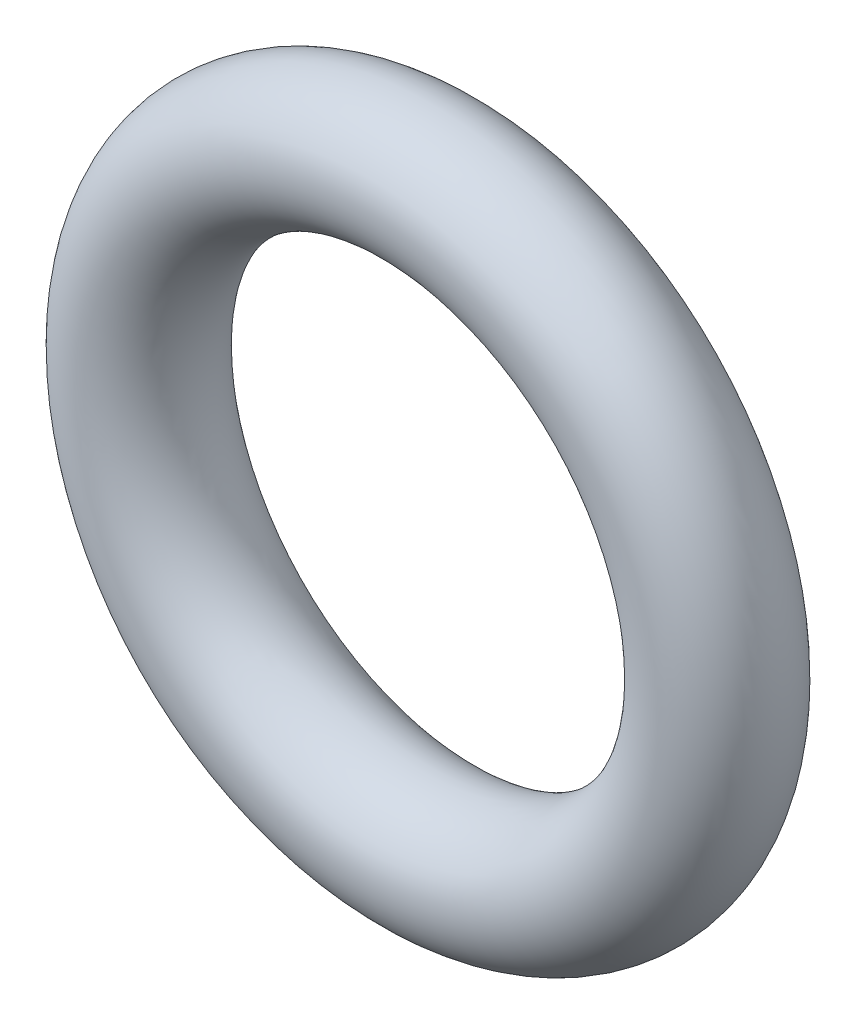
SolidWorks part; units mm, degrees
material "Rubber"
ref_plane "Front" through (0, 0, 0) normal (0, 0, 1) x (1, 0, 0)
ref_plane "Top" through (0, 0, 0) normal (0, 1, 0) x (1, 0, 0)
ref_plane "Right" through (0, 0, 0) normal (1, 0, 0) x (0, 0, -1)
sketch "Sketch1" plane through (0, 0, 0) normal (1, 0, 0) x (0, -1, 0)
  line L0 (0, -0.889) -> (0, 0.889) construction
  line L2 (-5.2946, 0) -> (5.2946, 0) construction
  line L3 (-3.0353, 0) -> (3.0353, 0) construction
  circle A0 centre (3.9243, 0) radius 0.889
  point P9 (3.0353, 0)
  point P10 (4.8133, 0)
  point P13 (3.9243, 0.889)
  point P14 (3.9243, -0.889)
  dimension "Width" = 1.778
  dimension "ID" = 6.0706
revolve "Revolve1" add sketch "Sketch1" angle 360 about L0
ref_axis "center_axis" through (0, 0, -0.9779) along (0, 0, 1)
